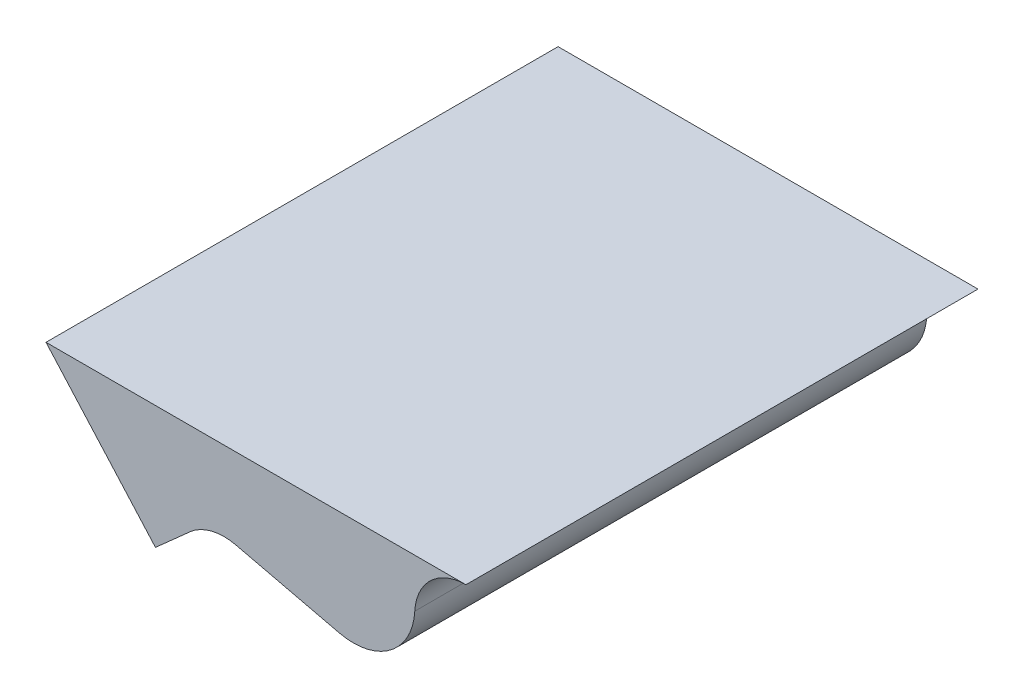
SolidWorks part; units mm, degrees
ref_plane "Plane1" through (0, 0, 0) normal (0, 0, 1) x (1, 0, 0)
ref_plane "Plane2" through (0, 0, 0) normal (0, 1, 0) x (1, 0, 0)
ref_plane "Plane3" through (0, 0, 0) normal (1, 0, 0) x (0, 0, -1)
sketch "Sketch1" plane through (0, 0, 0) normal (0, 0, 1) x (1, 0, 0)
  line L0 (-25, 5) -> (25, 5)
  line L1 (-25, 5) -> (-25, 0)
  line L2 (25, 0) -> (-25, 0)
  line L3 (25, 0) -> (25, 5)
  line L4 (0, 5) -> (0, 0) construction
  line L5 (50, 0) -> (-50, 0) construction
  dimension "D1" = 50
  dimension "D2" = 5
extrude "Base-Extrude" add sketch "Sketch1" along normal mid plane 50
sketch "Lance Tool sketch" plane through (0, 0, 0) normal (0, 0, 1) x (1, 0, 0)
  line L0 (9, 0) -> (-9, 0)
  line L1 (9, 0) -> (9, -6)
  line L2 (9, -6) -> (-1, -3.6344)
  line L3 (-1, -3.6344) -> (-3.6559, -6)
  line L4 (-3.6559, -6) -> (-9, 0)
  line L5 (25, 0) -> (-25, 0) construction
  line L6 (0, 0) -> (0, -3.871) construction
  dimension "Height from Drop Face" = 6
  dimension "Opening Width" = 18
  dimension "Form width" = 10
  dimension "Bend Angle" = 125
extrude "Lance Tool" add sketch "Lance Tool sketch" along normal mid plane 25
fillet "Inside Fillet" radius 2.5 2 edges at (9, 0, 0) (-1, -3.6344, 0)
fillet "Round" radius 3 1 edges at (9, -6, 0)
sketch "Sketch3" plane through (25, 0, 0) normal (1, 0, 0) x (0, 0, -1)
  line L4 (25, 5) -> (-25, 5)
  line L5 (-25, 5) -> (-25, 0)
  line L6 (-25, 0) -> (25, 0)
  line L7 (25, 0) -> (25, 5)
  line L8 (25, 5) -> (-25, 5)
  line L9 (-25, 5) -> (-25, 0)
  line L10 (-25, 0) -> (25, 0)
  line L11 (25, 0) -> (25, 5)
  dimension "D1" = 0
extrude "Cleanup Cut" cut sketch "Sketch3" against normal through all
sketch "Orientation sketch" plane through (0, 0, 0) normal (0, 1, 0) x (-1, 0, 0)
  line L4 (9, -12.5) -> (9, 12.5)
  line L5 (9, 12.5) -> (-11.5, 12.5)
  line L6 (-11.5, 12.5) -> (-11.5, -12.5)
  line L7 (-11.5, -12.5) -> (9, -12.5)
  line L8 (9, -12.5) -> (9, 12.5)
  line L9 (9, 12.5) -> (-11.5, 12.5)
  line L10 (-11.5, 12.5) -> (-11.5, -12.5)
  line L11 (-11.5, -12.5) -> (9, -12.5)
  dimension "D1" = 0
